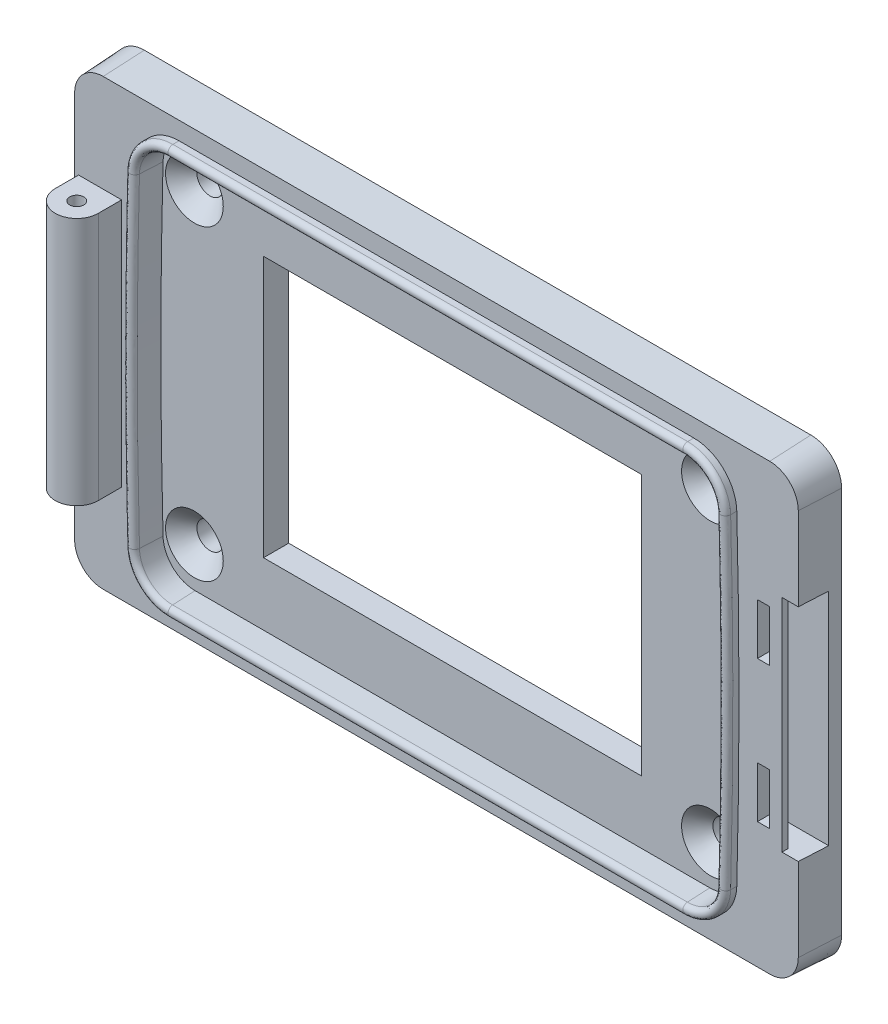
SolidWorks part; units mm, degrees
material "ﾅｲﾛﾝ 101"
ref_plane "正面" through (0, 0, 0) normal (0, 0, 1) x (1, 0, 0)
ref_plane "平面" through (0, 0, 0) normal (0, 1, 0) x (1, 0, 0)
ref_plane "右側面" through (0, 0, 0) normal (1, 0, 0) x (0, 0, -1)
sketch "ｽｹｯﾁ1" plane through (0, 0, 0) normal (0, 0, 1) x (1, 0, 0)
  line L0 (0, 0) -> (0, -46915.4499) construction
  line L1 (0, 0) -> (46915.4499, 0) construction
  line L2 (-59.25, -31.5) -> (-59.25, 31.5)
  line L3 (-54.25, 36.5) -> (54.25, 36.5)
  line L4 (-41.8954, 31.25) -> (41.8954, 31.25)
  line L5 (-54.25, -36.5) -> (54.25, -36.5)
  line L6 (41.8954, -31.25) -> (-41.8954, -31.25)
  line L7 (59.25, -31.5) -> (59.25, 31.5)
  line L8 (-30.75, 21.25) -> (-30.75, -21.25)
  line L9 (-30.75, -21.25) -> (30.75, -21.25)
  line L10 (30.75, -21.25) -> (30.75, 21.25)
  line L11 (30.75, 21.25) -> (-30.75, 21.25)
  line L12 (-41.8954, 33.25) -> (41.8954, 33.25)
  line L13 (41.8954, -33.25) -> (-41.8954, -33.25)
  line L14 (52.25, 15.65) -> (52.25, 7.35)
  line L15 (52.25, 7.35) -> (54.25, 7.35)
  line L16 (54.25, 7.35) -> (54.25, 15.65)
  line L17 (54.25, 15.65) -> (52.25, 15.65)
  line L18 (54.25, -15.65) -> (52.25, -15.65)
  line L19 (54.25, -7.35) -> (54.25, -15.65)
  line L20 (52.25, -7.35) -> (54.25, -7.35)
  line L21 (52.25, -15.65) -> (52.25, -7.35)
  arc A0 (-46.8936, -26.3851) -> (-46.8936, 26.3851) centre (929.5625, 0) cw
  arc A1 (46.8936, -26.3851) -> (46.8936, 26.3851) centre (-929.5625, 0) ccw
  arc A2 (54.25, -36.5) -> (59.25, -31.5) centre (54.25, -31.5) ccw
  arc A3 (54.25, 36.5) -> (59.25, 31.5) centre (54.25, 31.5) cw
  arc A4 (-59.25, 31.5) -> (-54.25, 36.5) centre (-54.25, 31.5) cw
  arc A5 (-41.8954, -31.25) -> (-46.8936, -26.3851) centre (-41.8954, -26.25) cw
  arc A6 (46.8936, -26.3851) -> (41.8954, -31.25) centre (41.8954, -26.25) cw
  arc A7 (41.8954, 31.25) -> (46.8936, 26.3851) centre (41.8954, 26.25) cw
  arc A8 (-41.8954, 31.25) -> (-46.8936, 26.3851) centre (-41.8954, 26.25) ccw
  arc A9 (-59.25, -31.5) -> (-54.25, -36.5) centre (-54.25, -31.5) ccw
  arc A10 (41.8954, 33.25) -> (48.8929, 26.4391) centre (41.8954, 26.25) cw
  arc A11 (48.8929, -26.4391) -> (48.8929, 26.4391) centre (-929.5625, 0) ccw
  arc A12 (48.8929, -26.4391) -> (41.8954, -33.25) centre (41.8954, -26.25) cw
  arc A13 (-41.8954, -33.25) -> (-48.8929, -26.4391) centre (-41.8954, -26.25) cw
  arc A14 (-48.8929, -26.4391) -> (-48.8929, 26.4391) centre (929.5625, 0) cw
  arc A15 (-41.8954, 33.25) -> (-48.8929, 26.4391) centre (-41.8954, 26.25) ccw
  circle A16 centre (-42, 25) radius 3.75
  circle A17 centre (-42, -25) radius 3.75
  circle A18 centre (42, -25) radius 3.75
  circle A19 centre (42, 25) radius 3.75
  point P25 (59.25, 36.5)
  point P28 (-59.25, 36.5)
  point P35 (46.75, 31.25)
  point P38 (-46.75, 31.25)
  point P41 (-59.25, -36.5)
  point P62 (-42, 25)
  point P63 (42, -25)
  point P64 (42, 25)
  point P65 (-42, -25)
  dimension "D3" = 62.5
  dimension "D4" = 93.5
  dimension "D5" = 94.5
  dimension "D8" = 5
  dimension "D9" = 5
  dimension "D17" = 7.5
  dimension "D1" = 118.5
  dimension "D2" = 73
  dimension "D6" = 61.5
  dimension "D7" = 42.5
  dimension "D11" = 5
  dimension "D12" = 2
  dimension "D13" = 8.3
  dimension "D14" = 14.7
  dimension "D15" = 50
  dimension "D16" = 84
  dimension "D10" = 2
extrude "ﾎﾞｽ - 押し出し1" add sketch "ｽｹｯﾁ1" along normal blind 8.5 draft 3 contours L3 A3 L7 A2 L5 A9 L2 A4 | L4 A7 A1 A6 L6 A5 A0 A8
extrude "ｶｯﾄ - 押し出し1" cut sketch "ｽｹｯﾁ1<3>" along normal through all from offset 6.7 contours L3 A3 L7 A2 L5 A9 L2 A4 | A15 A14 A13 L13 A12 A11 A10 L12
sketch "ｽｹｯﾁ1<3>" plane through (0, 0, 0) normal (0, 0, 1) x (1, 0, 0) same geometry as "ｽｹｯﾁ1"
sketch "ｽｹｯﾁ2" plane through (0, 0, 0) normal (0, 1, 0) x (1, 0, 0)
  line L0 (58.8989, -6.7) -> (59.1452, -2)
  line L1 (59.1452, -2) -> (49.452, -2)
  line L4 (49.452, -4.7) -> (49.452, -2)
  line L6 (59.25, 0) -> (58.8989, -6.7) construction
  line L7 (58.8989, -6.7) -> (56.25, -6.7)
  line L8 (56.25, -6.7) -> (56.25, -5.7)
  line L9 (56.25, -5.7) -> (55.25, -4.7)
  line L10 (55.25, -4.7) -> (49.452, -4.7)
  line L11 (-51.25, 0) -> (-51.25, -10.5)
  line L12 (-58.25, -10.5) -> (-58.25, 0)
  line L13 (-58.25, 0) -> (-51.25, 0)
  arc A0 (-58.25, -10.5) -> (-51.25, -10.5) centre (-54.75, -10.5) ccw
  circle A1 centre (-54.75, -10.5) radius 1.15
  dimension "D8" = 7
  dimension "D11" = 2.3
  dimension "D1" = 10
  dimension "D2" = 2
  dimension "D3" = 1
  dimension "D4" = 1
  dimension "D5" = 3
  dimension "D6" = 2
  dimension "D9" = 1
  dimension "D10" = 14
extrude "ﾎﾞｽ - 押し出し2" add sketch "ｽｹｯﾁ2" along normal mid plane 40.5 contours A0 L11 L13 L12 | A1
extrude "ｶｯﾄ - 押し出し2" cut sketch "ｽｹｯﾁ2<3>" against normal mid plane 35.9 contours L7 L8 L9 L10 L4 L1 L0
sketch "ｽｹｯﾁ2<3>" plane through (0, 0, 0) normal (0, 1, 0) x (1, 0, 0) same geometry as "ｽｹｯﾁ2"
extrude "ｶｯﾄ - 押し出し3" cut sketch "ｽｹｯﾁ1<5>" along normal through all from offset 2 contours L15 L16 L17 L14 | L20 L19 L18 L21
sketch "ｽｹｯﾁ1<5>" plane through (0, 0, 0) normal (0, 0, 1) x (1, 0, 0) same geometry as "ｽｹｯﾁ1"
extrude "ﾎﾞｽ - 押し出し3" add sketch "ｽｹｯﾁ1<6>" along normal blind 4.1 contours A14 A15 L12 A10 A11 A12 L13 A13 | L11 L8 L9 L10
sketch "ｽｹｯﾁ1<6>" plane through (0, 0, 0) normal (0, 0, 1) x (1, 0, 0) same geometry as "ｽｹｯﾁ1"
extrude "ﾎﾞｽ - 押し出し4" add sketch "ｽｹｯﾁ1<7>" against normal blind 5 contours A17 | A16 | A18 | A19
sketch "ｽｹｯﾁ1<7>" plane through (0, 0, 0) normal (0, 0, 1) x (1, 0, 0) same geometry as "ｽｹｯﾁ1"
hole_wizard "M4 丸皿ねじ用皿穴1" positions "3Dｽｹｯﾁ1" profile "ｽｹｯﾁ3" countersink size "M4" standard "JIS" end condition through all
sketch3d "3Dｽｹｯﾁ1"
  point P0 (-42, 25, 4.1)
  point P2 (42, 25, 4.1)
  point P4 (42, -25, 4.1)
  point P6 (-42, -25, 4.1)
sketch "ｽｹｯﾁ3" plane through (-42, 25, 4.1) normal (1, 0, 0) x (0, -1, 0)
  line L0 (0, 0) -> (0, 9.1)
  line L1 (0, 9.1) -> (2.15, 9.1)
  line L2 (2.15, 9.1) -> (2.15, 2.55)
  line L3 (2.15, 2.55) -> (4.7, 0)
  line L5 (4.7, 0) -> (0, 0)
  line L6 (-2.15, 2.55) -> (-4.7, 0) construction
  line L11 (0, -6.35) -> (0, 107.95) construction
  dimension "通し穴の直径" = 4.3
  dimension "通し穴の深さ" = 9.1
  dimension "表面の皿穴の直径" = 9.4
  dimension "表面の皿穴の角度" = 90
fillet "ﾌｨﾚｯﾄ1" 2 edges at (0, 33.25, 8.5) (0, 31.6955, 8.5) type full round first side face at (0, 33.25, 7.6) second side face at (0, 31.5802, 6.3) middle face at (0, 0, 8.5)
